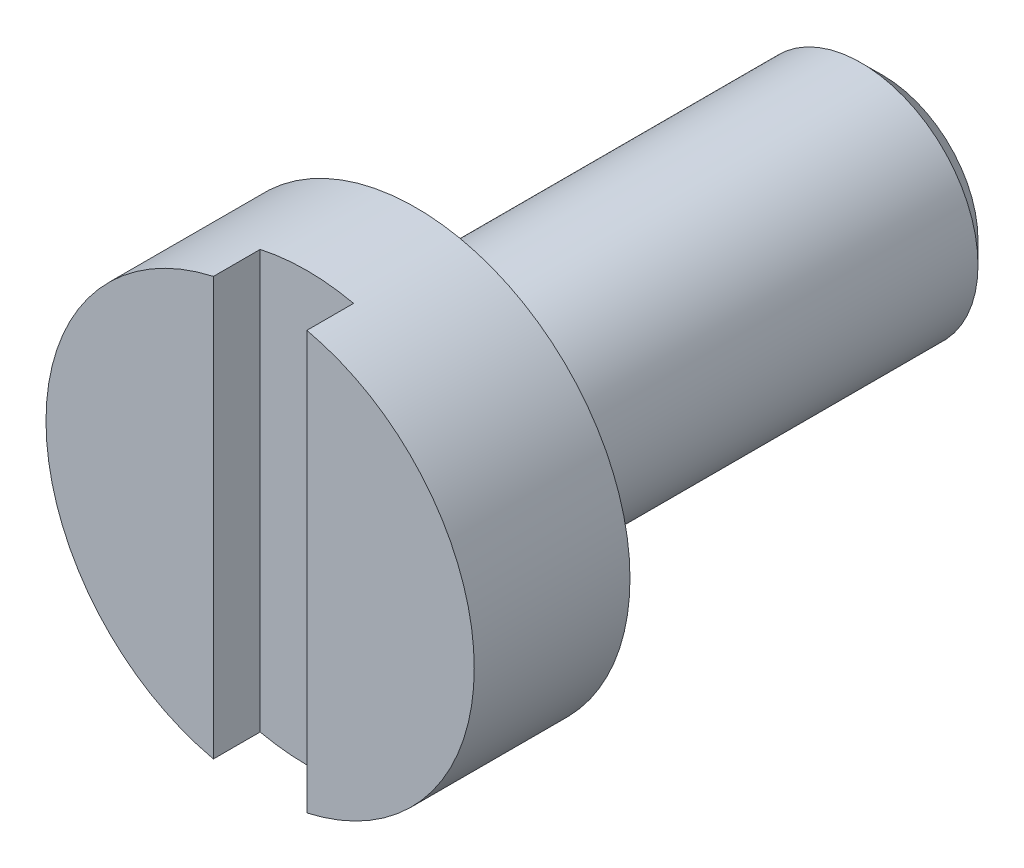
SolidWorks part; units mm, degrees
material "Сталь"
ref_plane "Спереди" through (0, 0, 0) normal (0, 0, 1) x (1, 0, 0)
ref_plane "Сверху" through (0, 0, 0) normal (0, 1, 0) x (1, 0, 0)
ref_plane "Справа" through (0, 0, 0) normal (1, 0, 0) x (0, 0, -1)
sketch "Эскиз1" plane through (0, 0, 0) normal (0, 0, 1) x (1, 0, 0)
  circle A0 centre (0, 0) radius 2.75
  dimension "D1" = 5.5
extrude "Бобышка-Вытянуть1" add sketch "Эскиз1" along normal blind 2
sketch "Эскиз2" plane through (0, 0, 0) normal (0, 0, -1) x (-1, 0, 0)
  circle A0 centre (0, 0) radius 1.5
  dimension "D1" = 3
extrude "Бобышка-Вытянуть2" add sketch "Эскиз2" along normal blind 6
cosmetic thread "Условное изображение резьбы1" parameters "D1"=6, "D2"=2.439
chamfer "Фаска1" distance 0.2805 angle 45 1 edges at (-1.5, 0, -6)
sketch "Эскиз3" plane through (0, 0, 0) normal (0, 1, 0) x (1, 0, 0)
  line L0 (-2.75, -2) -> (2.75, -2) construction
  line L1 (-0.6, -1.4) -> (0.6, -1.4)
  line L2 (-0.6, -1.4) -> (-0.6, -2.6)
  line L3 (-0.6, -2.6) -> (0.6, -2.6)
  line L4 (0.6, -1.4) -> (0.6, -2.6)
  line L5 (-0.6, -1.4) -> (0.6, -2.6) construction
  line L6 (-0.6, -2.6) -> (0.6, -1.4) construction
  point P0 (0, -2)
  dimension "D1" = 0.6
  dimension "D2" = 1.2
extrude "Вырез-Вытянуть1" cut sketch "Эскиз3" against normal blind 38 and the other way blind 38
